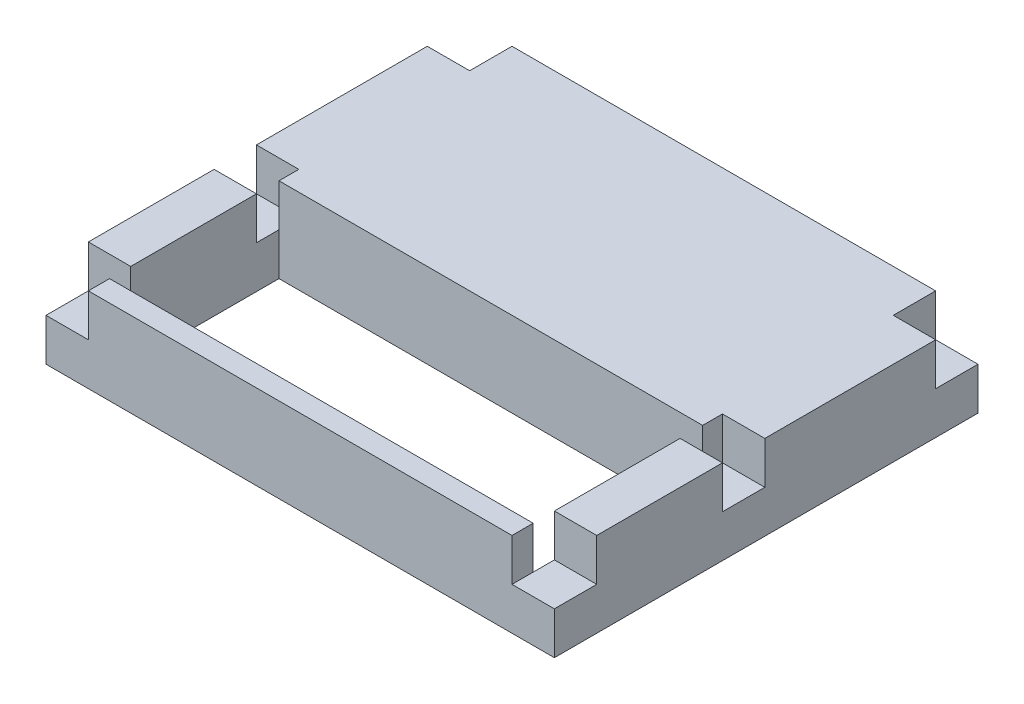
SolidWorks part; units mm, degrees
ref_plane "Front Plane" through (0, 0, 0) normal (0, 0, 1) x (1, 0, 0)
ref_plane "Top Plane" through (0, 0, 0) normal (0, 1, 0) x (1, 0, 0)
ref_plane "Right Plane" through (0, 0, 0) normal (1, 0, 0) x (0, 0, -1)
sketch "Sketch1" plane through (0, 0, 0) normal (0, 1, 0) x (1, 0, 0)
  line L1 (-60, 50) -> (60, 50)
  line L2 (-60, 50) -> (-60, -50)
  line L3 (-60, -50) -> (60, -50)
  line L4 (60, 50) -> (60, -50)
  line L5 (-60, 50) -> (60, -50) construction
  line L6 (-60, -50) -> (60, 50) construction
  point P0 (0, 0)
  dimension "D1" = 120
  dimension "D2" = 100
extrude "Boss-Extrude1" add sketch "Sketch1" along normal blind 20
sketch "Sketch5" plane through (0, 20, 0) normal (0, 1, 0) x (1, 0, 0)
  line L0 (-60, 50) -> (60, 50)
  line L1 (60, 50) -> (60, -50)
  line L2 (60, -50) -> (-60, -50)
  line L3 (-60, -50) -> (-60, 50)
  line L4 (-60, 0) -> (60, 0)
  line L5 (60, 0) -> (60, -50)
  line L6 (-60, 0) -> (-60, -50)
  line L7 (-60, 50) -> (-60, 0)
  line L8 (60, 50) -> (60, 0)
  line L9 (-60, 25) -> (-40, 25)
  line L10 (-40, 25) -> (-40, 30)
  line L11 (-40, 25) -> (-40, 20)
  line L12 (-40, 20) -> (-60, 20)
  line L13 (-40, 30) -> (-60, 30)
  line L14 (60, 30) -> (50, 30)
  line L15 (50, 30) -> (50, 20)
  line L16 (50, 20) -> (60, 20)
  line L17 (60, 20) -> (60, 30)
  line L18 (55, 20) -> (55, 25)
  line L19 (-60, 0) -> (-55, 0)
  line L20 (52, 28) -> (58, 28)
  line L21 (52, 28) -> (52, 22)
  line L22 (52, 22) -> (58, 22)
  line L23 (58, 28) -> (58, 22)
  line L24 (52, 28) -> (58, 22) construction
  line L25 (52, 22) -> (58, 28) construction
  line L26 (-53, 28) -> (-47, 28)
  line L27 (-53, 28) -> (-53, 22)
  line L28 (-53, 22) -> (-47, 22)
  line L29 (-47, 28) -> (-47, 22)
  line L30 (-53, 28) -> (-47, 22) construction
  line L31 (-53, 22) -> (-47, 28) construction
  line L32 (-55, 0) -> (-55, -5)
  line L33 (-55, -5) -> (-60, -5)
  line L34 (-60, -5) -> (-60, 0)
  line L35 (-60, -2.5) -> (-55, -2.5)
  line L36 (-60, -50) -> (-60, -45)
  line L37 (-60, -45) -> (-55, -45)
  line L38 (-55, -45) -> (-55, -50)
  line L39 (-55, -50) -> (-60, -50)
  line L40 (-60, -47.5) -> (-55, -47.5)
  line L41 (60, -50) -> (60, -45)
  line L42 (60, -45) -> (55, -45)
  line L43 (55, -45) -> (55, -50)
  line L44 (55, -50) -> (60, -50)
  line L45 (60, -47.5) -> (55, -47.5)
  line L46 (60, 0) -> (55, 0)
  line L47 (55, 0) -> (55, -5)
  line L48 (55, -5) -> (60, -5)
  line L49 (60, -5) -> (60, 0)
  line L50 (60, -2.5) -> (55, -2.5)
  line L52 (56, -1) -> (59, -1)
  line L53 (56, -1) -> (56, -4)
  line L54 (56, -4) -> (59, -4)
  line L55 (59, -1) -> (59, -4)
  line L56 (56, -1) -> (59, -4) construction
  line L57 (56, -4) -> (59, -1) construction
  line L58 (-59, -1) -> (-56, -1)
  line L59 (-59, -1) -> (-59, -4)
  line L60 (-59, -4) -> (-56, -4)
  line L61 (-56, -1) -> (-56, -4)
  line L62 (-59, -1) -> (-56, -4) construction
  line L63 (-59, -4) -> (-56, -1) construction
  line L64 (-59, -46) -> (-56, -46)
  line L65 (-59, -46) -> (-59, -49)
  line L66 (-59, -49) -> (-56, -49)
  line L67 (-56, -46) -> (-56, -49)
  line L68 (-59, -46) -> (-56, -49) construction
  line L69 (-59, -49) -> (-56, -46) construction
  line L70 (56, -46) -> (59, -46)
  line L71 (56, -46) -> (56, -49)
  line L72 (56, -49) -> (59, -49)
  line L73 (59, -46) -> (59, -49)
  line L74 (56, -46) -> (59, -49) construction
  line L75 (56, -49) -> (59, -46) construction
  point P26 (-50, 25)
  point P51 (57.5, -2.5)
  point P56 (-57.5, -2.5)
  point P61 (-57.5, -47.5)
  point P66 (57.5, -47.5)
  dimension "D1" = 6
  dimension "D2" = 6
  dimension "D3" = 10
  dimension "D4" = 10
  dimension "D5" = 5
  dimension "D6" = 6
  dimension "D7" = 6
  dimension "D8" = 3
  dimension "D9" = 3
  dimension "D10" = 5
  dimension "D11" = 5
  dimension "D12" = 5
  dimension "D13" = 5
  dimension "D14" = 3
  dimension "D15" = 3
  dimension "D16" = 3
  dimension "D17" = 5
  dimension "D18" = 5
  dimension "D19" = 3
  dimension "D20" = 5
  dimension "D21" = 5
  dimension "D22" = 3
  dimension "D23" = 3
sketch "Sketch6" plane through (0, 0, 0) normal (0, -1, 0) x (1, 0, 0)
  line L0 (-60, 50) -> (60, 50)
  line L1 (60, 50) -> (60, 0)
  line L2 (60, 0) -> (-60, 0)
  line L3 (-60, 0) -> (-60, 50)
  line L4 (-55, 5) -> (-55, 45)
  line L5 (-55, 45) -> (55, 45)
  line L6 (55, 45) -> (55, 5)
  line L7 (55, 5) -> (-55, 5)
  line L8 (-55, 45) -> (-50, 45)
  line L9 (-50, 45) -> (-50, 5)
  line L10 (-50, 5) -> (-55, 5)
  line L11 (-55, 45) -> (-55, 5)
  line L12 (-55, 45) -> (-50, 45)
  line L13 (55, 45) -> (50, 45)
  line L14 (50, 45) -> (50, 5)
  line L15 (50, 5) -> (55, 5)
  line L16 (55, 45) -> (55, 5)
  line L17 (50, 45) -> (55, 45)
  dimension "D1" = 5
extrude "Cut-Extrude1" cut sketch "Sketch6" against normal blind 20 contours L5 L6 L7 L4
sketch "Sketch7" plane through (60, 0, 0) normal (1, 0, 0) x (0, 0, -1)
  line L0 (50, 0) -> (-50, 0)
  line L1 (-50, 0) -> (-50, 20)
  line L2 (-50, 20) -> (50, 20)
  line L3 (50, 20) -> (50, 0)
  line L4 (-50, 20) -> (-50, 118.2899)
  line L5 (-50, 118.2899) -> (0, 118.2899)
  line L6 (0, 118.2899) -> (0, 20)
  line L7 (-50, 20) -> (0, 20)
  line L8 (0, 20) -> (-35.7746, 118.2899)
  line L9 (-17.8873, 69.1449) -> (-27.2842, 65.7247)
  line L10 (-27.2842, 65.7247) -> (-17.8873, 69.1449)
  line L11 (50, 118.2899) -> (50, 20)
  line L12 (-50, 20) -> (-45, 20)
  line L13 (-27.2842, 65.7247) -> (-46.4164, 118.2899)
  line L14 (-46.4164, 118.2899) -> (-10.6418, 20)
  line L15 (-45, 25) -> (-45, 114.3984)
  line L16 (-34.3582, 114.3984) -> (0, 114.3984)
  line L17 (-50, 20) -> (-50, 25)
  line L18 (-45, 25) -> (-12.4616, 25)
  line L19 (-1.8199, 25) -> (0, 25)
  line L20 (-45, 25) -> (-45, 20)
  line L21 (0, 118.2899) -> (50, 118.2899)
  line L22 (50, 118.2899) -> (50, 20)
  line L23 (0, 20) -> (0, 118.2899)
  line L24 (50, 20) -> (0, 20)
  line L25 (-17.8873, 69.1449) -> (-14.4671, 59.748)
  line L26 (-14.4671, 59.748) -> (35, 77.7526)
  line L27 (-17.8873, 69.1449) -> (-21.3075, 78.5419)
  line L28 (-21.3075, 78.5419) -> (35, 99.0361)
  line L31 (25, 20) -> (35, 20)
  line L32 (35, 20) -> (35, 118.2899)
  line L33 (25, 20) -> (15, 20)
  line L34 (15, 20) -> (15, 118.2899)
  line L35 (-10.6418, 20) -> (-1.2449, 23.4202)
  line L36 (-35.7746, 118.2899) -> (-45.1715, 114.8697)
  line L37 (-40.4731, 116.5798) -> (-5.9433, 21.7101)
  dimension "D1" = 70
sketch "Sketch13" plane through (-60, 0, 0) normal (-1, 0, 0) x (0, 0, 1)
  line L0 (-50, 20) -> (-50, 118.2899)
  line L1 (-50, 118.2899) -> (50, 118.2899)
  line L2 (50, 118.2899) -> (50, 20)
  line L3 (50, 20) -> (-50, 20)
  line L4 (-35, 118.2899) -> (-35, 20)
  line L5 (-35, 20) -> (-15, 20)
  line L6 (-15, 20) -> (-15, 118.2899)
  line L7 (46.4164, 118.2899) -> (10.6418, 20)
  line L8 (1.2449, 23.4202) -> (10.6418, 20)
  line L9 (0, 20) -> (35.7746, 118.2899)
  line L10 (35.7746, 118.2899) -> (45.1715, 114.8697)
  line L11 (40.4731, 116.5798) -> (5.9433, 21.7101)
  line L12 (12.4616, 25) -> (45, 25)
  line L13 (45, 25) -> (45, 114.3984)
  line L14 (0, 118.2899) -> (0, 20)
  line L15 (0, 25) -> (1.8199, 25)
  line L16 (-35, 99.0361) -> (21.3075, 78.5419)
  line L17 (-35, 77.7526) -> (14.4671, 59.748)
  line L18 (0, 114.3984) -> (34.3582, 114.3984)
extrude "Boss-Extrude4" add sketch "Sketch6<3>" against normal blind 20 contours L9 L5 L4 L7 | L5 L14 L7 L6 region at (-52.5, 0, 25) region at (52.5, 0, 25)
sketch "Sketch6<3>" plane through (0, 0, 0) normal (0, -1, 0) x (1, 0, 0) same geometry as "Sketch6"
sketch "Sketch14" plane through (0, 20, 0) normal (0, 1, 0) x (1, 0, 0)
  line L0 (60, 0) -> (60, -10.6418)
  line L1 (60, -10.6418) -> (50, -10.6418)
  line L2 (50, -45) -> (50, -5) construction
  line L3 (50, -10.6418) -> (50, 0)
  line L4 (50, 0) -> (60, 0)
  line L5 (55, -10.6418) -> (55, -5.3209)
  line L6 (55, -5.3209) -> (60, -5.3209)
  line L7 (60, -5.3209) -> (60, -10.3209)
  line L8 (0, 0) -> (0, 20.8987)
  line L9 (50, -0.3209) -> (60, -0.3209)
  line L10 (50, -0.3209) -> (50, -10.3209)
  line L11 (50, -10.3209) -> (60, -10.3209)
  line L12 (60, -0.3209) -> (60, -10.3209)
  line L13 (50, -0.3209) -> (60, -10.3209) construction
  line L14 (50, -10.3209) -> (60, -0.3209) construction
  line L15 (-50, -10.3209) -> (-60, -0.3209) construction
  line L16 (-50, -0.3209) -> (-60, -10.3209) construction
  line L17 (-60, -0.3209) -> (-60, -10.3209)
  line L18 (-50, -10.3209) -> (-60, -10.3209)
  line L19 (-50, -0.3209) -> (-50, -10.3209)
  line L20 (-50, -0.3209) -> (-60, -0.3209)
  line L21 (-60, -5.3209) -> (-60, -10.3209)
  line L22 (-55, -5.3209) -> (-60, -5.3209)
  line L23 (-55, -10.6418) -> (-55, -5.3209)
  line L24 (-50, 0) -> (-60, 0)
  line L25 (-50, -10.6418) -> (-50, 0)
  line L26 (-60, -10.6418) -> (-50, -10.6418)
  line L27 (-60, 0) -> (-60, -10.6418)
  line M3 (50, -5) -> (50, -45)
  line M5 (-50, -45) -> (-50, -5)
  line M8 (-60, 50) -> (-60, -50)
extrude "Cut-Extrude2" cut sketch "Sketch14" against normal blind 10 contours L18 L23 L22 L17 | L23 L18 L19 L20 L22 M5 M8 | L11 L5 L6 L0 L9 L3 M3 | L5 L11 L0 L6 region at (54.1667, 20, 4.4876) region at (57.5, 20, 7.8209) region at (-54.1667, 20, 4.4876) region at (-57.5, 20, 7.8209)
sketch "Sketch15" plane through (0, 20, 0) normal (0, 1, 0) x (1, 0, 0)
  line L0 (-60, 50) -> (-50, 50)
  line L1 (-60, 50) -> (60, 50) construction
  line L2 (-50, 50) -> (-50, 40)
  line L3 (-50, 40) -> (-60, 40)
  line L4 (-60, -50) -> (-60, 50) construction
  line L5 (-60, 40) -> (-60, 50)
  line L6 (60, 50) -> (60, 40)
  line L7 (60, 50) -> (60, -50) construction
  line L8 (60, 40) -> (50, 40)
  line L9 (50, 40) -> (50, 50)
  line L10 (50, 50) -> (60, 50)
  line L11 (60, -50) -> (50, -50)
  line L12 (60, -50) -> (-60, -50) construction
  line L13 (50, -50) -> (50, -40)
  line L14 (50, -45) -> (50, -10.3209) construction
  line L15 (50, -40) -> (60, -40)
  line L16 (60, -40) -> (60, -50)
  line L17 (-60, -50) -> (-60, -40)
  line L18 (-60, -40) -> (-50, -40)
  line L19 (-50, -45) -> (-50, -10.3209) construction
  line L20 (-50, -40) -> (-50, -50)
  line L21 (-50, -50) -> (-60, -50)
extrude "Cut-Extrude3" cut sketch "Sketch15" against normal blind 10
sketch "Sketch16" plane through (0, 0, 0) normal (0, -1, 0) x (1, 0, 0)
  line L0 (-59, 46) -> (-56, 46)
  line L1 (-56, 46) -> (-56, 49)
  line L2 (-56, 49) -> (-59, 49)
  line L3 (-59, 49) -> (-59, 46)
  line L4 (-59, 4) -> (-56, 4)
  line L5 (-56, 4) -> (-56, 1)
  line L6 (-56, 1) -> (-59, 1)
  line L7 (-59, 1) -> (-59, 4)
  line L8 (56, 4) -> (59, 4)
  line L9 (59, 4) -> (59, 1)
  line L10 (59, 1) -> (56, 1)
  line L11 (56, 1) -> (56, 4)
  line L12 (56, 49) -> (59, 49)
  line L13 (59, 49) -> (59, 46)
  line L14 (59, 46) -> (56, 46)
  line L15 (56, 46) -> (56, 49)
  line L16 (52, -22) -> (58, -22)
  line L17 (58, -22) -> (58, -28)
  line L18 (58, -28) -> (52, -28)
  line L19 (52, -28) -> (52, -22)
  line L20 (0, 0) -> (0, -50)
  line L21 (-60, -50) -> (60, -50) construction
  line L22 (-58, -28) -> (-52, -28)
  line L23 (-52, -28) -> (-52, -22)
  line L24 (-58, -22) -> (-58, -28)
  line L25 (-52, -22) -> (-58, -22)
extrude "Cut-Extrude4" cut sketch "Sketch16" against normal blind 5 contours L2 L3 L0 L1 | L15 L14 L13 L12 | L7 L6 L5 L4 | L11 L10 L9 L8 | L19 L18 L17 L16 | L23 L25 L24 L22 region at (-57.5, 0, 47.5) region at (-57.5, 0, 2.5) region at (57.5, 0, 2.5) region at (57.5, 0, 47.5) region at (55, 0, -25) region at (-55, 0, -25)
